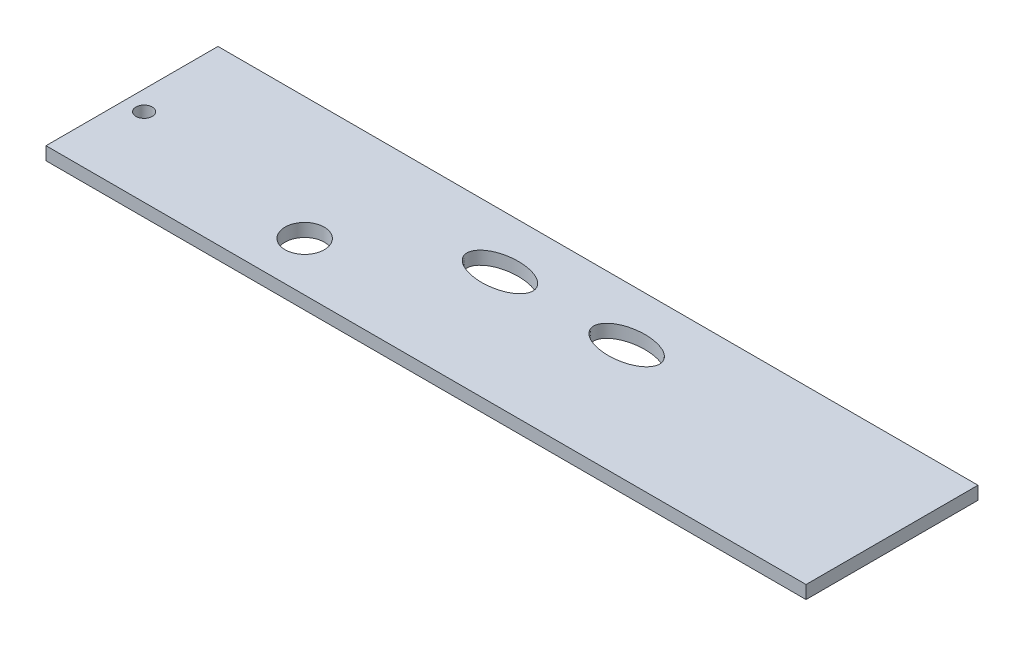
SolidWorks part; units mm, degrees
ref_plane "Front Plane" through (0, 0, 0) normal (0, 0, 1) x (1, 0, 0)
ref_plane "Top Plane" through (0, 0, 0) normal (0, 1, 0) x (1, 0, 0)
ref_plane "Right Plane" through (0, 0, 0) normal (1, 0, 0) x (0, 0, -1)
sketch "Sketch1" plane through (0, 0, 0) normal (0, 1, 0) x (1, 0, 0)
  line L1 (-71.1995, 6.7803) -> (45.0405, 6.7803)
  line L2 (-71.1995, 6.7803) -> (-71.1995, -3.2197)
  line L3 (1.581, -6.8197) -> (23.4406, -6.8197) construction
  line L4 (45.0405, 6.7803) -> (45.0405, -3.2197)
  line L5 (1.581, 3.2803) -> (27.3434, 3.2803) construction
  line L6 (-10.0795, -1.5197) -> (-0.3565, -1.5197) construction
  line L7 (-10.0795, -13.2197) -> (-10.0795, 1.7803) construction
  line L10 (-71.1995, -3.2197) -> (-71.1995, -19.5197)
  line L11 (-71.1995, -19.5197) -> (45.0405, -19.5197)
  line L12 (45.0405, -3.2197) -> (45.0405, -19.5197)
  circle A0 centre (-39.1395, -12.0197) radius 3
  circle A1 centre (-68.1995, -7.5197) radius 1.25
  spline S0 degree 3 poles (-4.3315, 0.6889) (-5.9996, -1.5197) (-4.3315, -3.7283) (-0.3935, -4.6154) (3.5444, -3.7283) (5.2125, -1.5197) (3.5444, 0.6889) (-0.3935, 1.576) (-4.3315, 0.6889) (-5.9996, -1.5197) (-4.3315, -3.7283) knots -2.356194 -1.570796 -0.785398 0 0.785398 1.570796 2.356194 3.141593 3.926991 4.712389 5.497787 6.283185 7.068583 7.853982 8.63938 only from (-5.4435, -1.5197) to (-5.4435, -1.5197)
  spline S1 degree 3 poles (-23.7035, 3.9889) (-25.3716, 1.7803) (-23.7035, -0.4283) (-19.7655, -1.3154) (-15.8276, -0.4283) (-14.1595, 1.7803) (-15.8276, 3.9889) (-19.7655, 4.876) (-23.7035, 3.9889) (-25.3716, 1.7803) (-23.7035, -0.4283) knots -2.356194 -1.570796 -0.785398 0 0.785398 1.570796 2.356194 3.141593 3.926991 4.712389 5.497787 6.283185 7.068583 7.853982 8.63938 only from (-24.8155, 1.7803) to (-24.8155, 1.7803) construction
  spline S2 degree 3 poles (-23.7035, 0.6889) (-25.3716, -1.5197) (-23.7035, -3.7283) (-19.7655, -4.6154) (-15.8276, -3.7283) (-14.1595, -1.5197) (-15.8276, 0.6889) (-19.7655, 1.576) (-23.7035, 0.6889) (-25.3716, -1.5197) (-23.7035, -3.7283) knots -2.356194 -1.570796 -0.785398 0 0.785398 1.570796 2.356194 3.141593 3.926991 4.712389 5.497787 6.283185 7.068583 7.853982 8.63938 only from (-24.8155, -1.5197) to (-24.8155, -1.5197)
  spline S3 degree 3 poles (-4.3315, 3.9889) (-5.9996, 1.7803) (-4.3315, -0.4283) (-0.3935, -1.3154) (3.5444, -0.4283) (5.2125, 1.7803) (3.5444, 3.9889) (-0.3935, 4.876) (-4.3315, 3.9889) (-5.9996, 1.7803) (-4.3315, -0.4283) knots -2.356194 -1.570796 -0.785398 0 0.785398 1.570796 2.356194 3.141593 3.926991 4.712389 5.497787 6.283185 7.068583 7.853982 8.63938 only from (-5.4435, 1.7803) to (-5.4435, 1.7803) construction
  dimension "D3" = 16.3
  dimension "D4" = 19.372
  dimension "D8" = 6
  dimension "D9" = 2.5
  dimension "D1" = 10
  dimension "D2" = 116.24
  dimension "D5" = 14.736
  dimension "D6" = 29.06
  dimension "D7" = 18.8
  dimension "D10" = 58.12
  dimension "D11" = 12
  dimension "D12" = 13.6
  dimension "D13" = 3.5
  dimension "D14" = 5.3
extrude "Boss-Extrude1" add sketch "Sketch1" along normal blind 2
